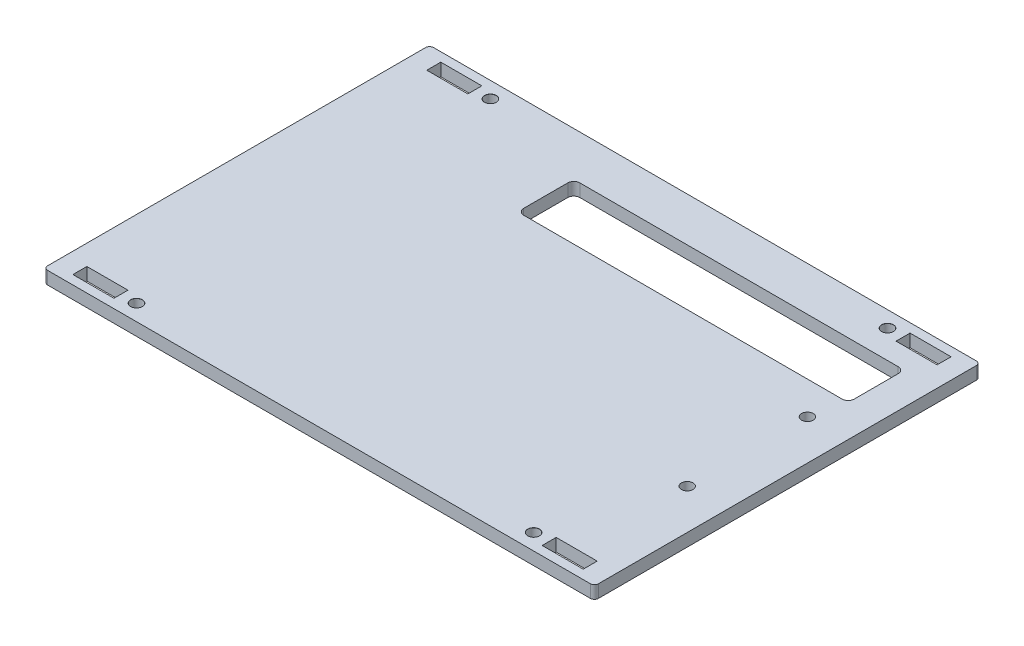
SolidWorks part; units mm, degrees
material "MDF"
ref_plane "Front Plane" through (0, 0, 0) normal (0, 0, 1) x (1, 0, 0)
ref_plane "Top Plane" through (0, 0, 0) normal (0, 1, 0) x (1, 0, 0)
ref_plane "Right Plane" through (0, 0, 0) normal (1, 0, 0) x (0, 0, -1)
sketch "Sketch1" plane through (0, 0, 0) normal (0, 1, 0) x (1, 0, 0)
  line L1 (-68.745, -48.1725) -> (68.745, -48.1725)
  line L2 (-68.745, -48.1725) -> (-68.745, 48.1725)
  line L3 (-68.745, 48.1725) -> (68.745, 48.1725)
  line L4 (68.745, -48.1725) -> (68.745, 48.1725)
  line L5 (-68.745, -48.1725) -> (68.745, 48.1725) construction
  line L6 (-68.745, 48.1725) -> (68.745, -48.1725) construction
  line L7 (-68.745, -44.1725) -> (68.745, -44.1725) construction
  line L8 (-68.745, -44.1725) -> (-68.745, 44.1725)
  line L9 (-68.745, 44.1725) -> (68.745, 44.1725) construction
  line L10 (68.745, -44.1725) -> (68.745, 44.1725)
  line L11 (-68.745, -44.1725) -> (68.745, 44.1725) construction
  line L12 (-68.745, 44.1725) -> (68.745, -44.1725) construction
  line L13 (-63.695, 42.4262) -> (-53.445, 42.4262)
  line L14 (-63.695, 42.4262) -> (-63.695, 45.9187)
  line L15 (-63.695, 45.9187) -> (-53.445, 45.9187)
  line L16 (-53.445, 42.4262) -> (-53.445, 45.9187)
  line L17 (-63.695, 42.4262) -> (-53.445, 45.9187) construction
  line L18 (-63.695, 45.9187) -> (-53.445, 42.4262) construction
  circle A0 centre (-49.57, 44.1725) radius 2.5
  point P0 (0, 0)
  point P6 (0, 0)
  point P11 (-58.57, 44.1725)
  dimension "D8" = 5
  dimension "D1" = 88.345
  dimension "D2" = 137.49
  dimension "D3" = 4
  dimension "D4" = 10.175
  dimension "D5" = 10.25
  dimension "D6" = 3.4925
  dimension "D7" = 19.175
extrude "Boss-Extrude1" add sketch "Sketch1" along normal blind 3.175 contours L1 L4 L3 L2 A0 L16 L13 L14 L15 | L13 L16 L15 L14 | A0 region at (0.2327, 0, 0.1856) region at (-58.57, 0, -44.1725) region at (-49.57, 0, -44.1725)
extrude "Cut-Extrude1" cut sketch "Sketch1<3>" against normal through all both and the other way through all contours L13 L16 L15 L14 region at (-58.57, 0, -44.1725)
sketch "Sketch1<3>" plane through (0, 0, 0) normal (0, 1, 0) x (1, 0, 0) same geometry as "Sketch1"
hole_wizard "M2.5 Clearance Hole1" positions "Sketch2" profile "Sketch3" hole size "M2.5" standard "ANSI Metric" end condition through all
sketch "Sketch2" plane through (0, 3.175, 0) normal (0, 1, 0) x (1, 0, 0)
  point P0 (-49.57, 44.1725)
sketch "Sketch3" plane through (-49.57, 3.175, -44.1725) normal (1, 0, 0) x (0, 0, 1)
  line L0 (0, 0) -> (0, 3.175)
  line L1 (0, 3.175) -> (1.45, 3.175)
  line L2 (1.45, 3.175) -> (1.45, 0.021)
  line L3 (1.45, 0.021) -> (1.475, 0)
  line L5 (1.475, 0) -> (0, 0)
  line L6 (-1.45, 0.021) -> (-1.475, 0) construction
  line L11 (0, -6.35) -> (0, 107.95) construction
  dimension "Thru Hole Dia." = 2.9
  dimension "Thru Hole Depth" = 3.175
  dimension "Near C'Sink Dia." = 2.95
  dimension "Near C'Sink Angle" = 100
mirror "Mirror1" about plane through (0, 0, 0) normal (1, 0, 0) of "M2.5 Clearance Hole1", "Cut-Extrude1" second plane through (0, 0, 0) second plane normal (0, 0, 1)
sketch "Sketch4" plane through (0, 3.175, 0) normal (0, 1, 0) x (1, 0, 0)
  line L0 (68.745, -48.1725) -> (68.745, 48.1725) construction
  line L1 (-21.745, 37.1725) -> (60.745, 37.1725)
  line L2 (-21.745, 37.1725) -> (-21.745, 23.1725)
  line L3 (-21.745, 23.1725) -> (60.745, 23.1725)
  line L4 (60.745, 37.1725) -> (60.745, 23.1725)
  line L5 (-68.745, -48.1725) -> (-68.745, 48.1725) construction
  line L6 (-68.745, 48.1725) -> (68.745, 48.1725) construction
  dimension "D1" = 8
  dimension "D2" = 47
  dimension "D3" = 11
  dimension "D4" = 14
extrude "Cut-Extrude2" cut sketch "Sketch4" against normal through all both and the other way through all
fillet "Fillet1" radius 1.5 4 edges at (-21.745, 1.5875, -23.1725) (60.745, 1.5875, -23.1725) (60.745, 1.5875, -37.1725) (-21.745, 1.5875, -37.1725)
fillet "Fillet2" radius 1 4 edges at (68.745, 1.5875, 48.1725) (-68.745, 1.5875, 48.1725) (-68.745, 1.5875, -48.1725) (68.745, 1.5875, -48.1725)
sketch "Sketch5" plane through (0, 3.175, 0) normal (0, 1, 0) x (1, 0, 0)
  line L0 (58.745, 15) -> (58.745, -15) construction
  line L1 (68.745, -47.1725) -> (68.745, 47.1725) construction
  point P0 (58.745, 15)
  point P1 (58.745, -15)
  point P2 (58.745, 0)
  point P10 (58.745, -15)
  point P12 (58.745, 15)
  dimension "D1" = 30
  dimension "D2" = 10
hole_wizard "M2.5 Clearance Hole2" positions "Sketch5" profile "Sketch6" hole size "M2.5" standard "ANSI Metric" end condition through all
sketch "Sketch6" plane through (58.745, 3.175, -15) normal (1, 0, 0) x (0, 0, 1)
  line L0 (0, 0) -> (0, 3.175)
  line L1 (0, 3.175) -> (1.45, 3.175)
  line L2 (1.45, 3.175) -> (1.45, 0)
  line L5 (1.45, 0) -> (0, 0)
  line L11 (0, -6.35) -> (0, 107.95) construction
  dimension "Thru Hole Dia." = 2.9
  dimension "Thru Hole Depth" = 3.175
